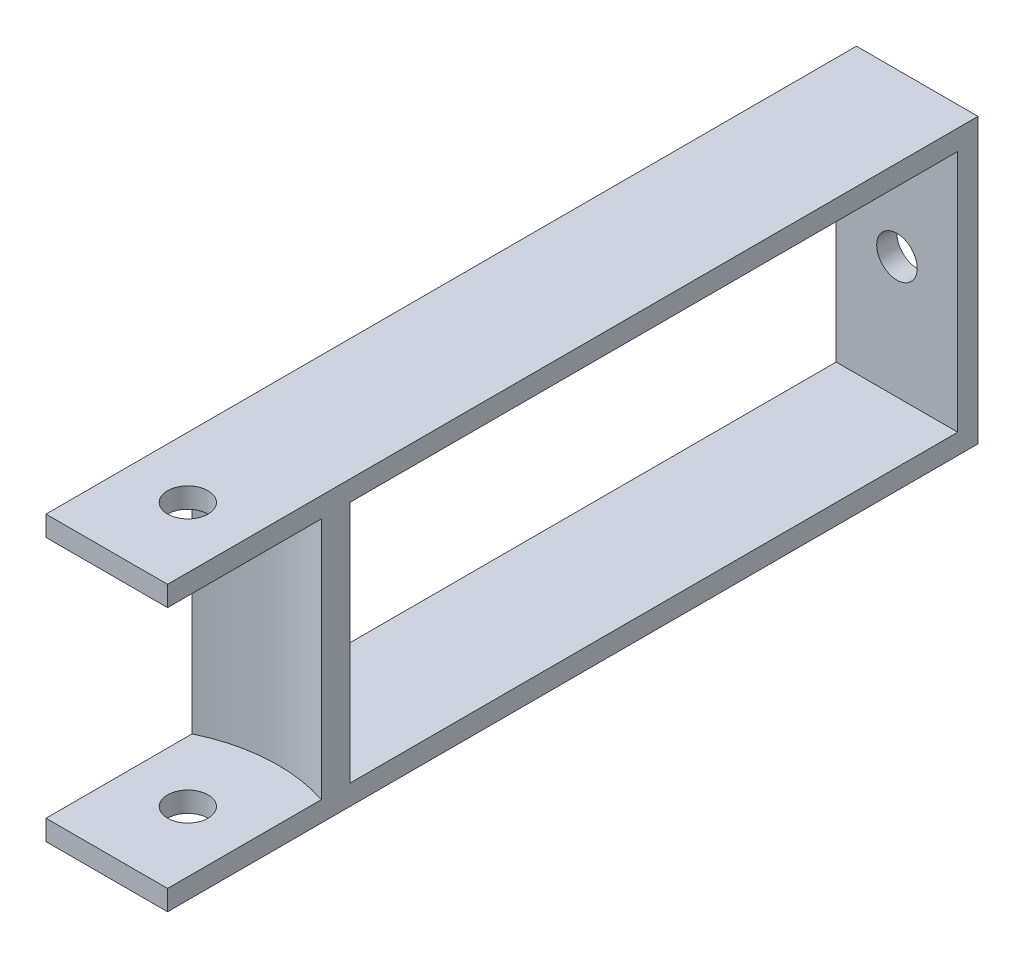
SolidWorks part; units mm, degrees
ref_plane "Alzado" through (0, 0, 0) normal (0, 0, 1) x (1, 0, 0)
ref_plane "Planta" through (0, 0, 0) normal (0, 1, 0) x (1, 0, 0)
ref_plane "Vista lateral" through (0, 0, 0) normal (1, 0, 0) x (0, 0, -1)
sketch "Croquis1" plane through (0, 0, 0) normal (0, 0, 1) x (1, 0, 0)
  line L1 (-10.0621, -21.7081) -> (19.9379, -21.7081)
  line L2 (-10.0621, -21.7081) -> (-10.0621, 48.2919)
  line L3 (-10.0621, 48.2919) -> (19.9379, 48.2919)
  line L4 (19.9379, -21.7081) -> (19.9379, 48.2919)
  dimension "D1" = 30
  dimension "D2" = 70
extrude "Saliente-Extruir1" add sketch "Croquis1" along normal blind 200
sketch "Croquis3" [suppressed] plane through (0, -21.7081, 0) normal (0, -1, 0) x (1, 0, 0)
  line L0 (19.9379, 200) -> (19.9379, 0) construction
  line L1 (-10.0621, 0) -> (19.9379, 0) construction
  circle A1 centre (4.9379, 180) radius 6.8739
  dimension "D1" = 15
  dimension "D2" = 180
extrude "Cortar-Extruir1" [suppressed] cut sketch "Croquis3" against normal through all contours A1
sketch "Croquis5" plane through (0, 0, 0) normal (0, 0, -1) x (-1, 0, 0)
  line L0 (-19.9379, -21.7081) -> (-19.9379, 48.2919) construction
  line L1 (10.0621, -21.7081) -> (-19.9379, -21.7081) construction
  circle A0 centre (-4.9379, 13.2919) radius 5
  dimension "D1" = 10
  dimension "D2" = 15
  dimension "D3" = 35
extrude "Cortar-Extruir2" cut sketch "Croquis5" against normal blind 20
ref_plane "Plano1" through (0, 13.2919, 0) normal (0, -1, 0) x (-1, 0, 0)
sketch "Croquis6" plane through (0, 13.2919, 0) normal (0, -1, 0) x (-1, 0, 0)
  line L0 (10.0621, -200) -> (-19.9379, -200) construction
  circle A0 centre (-7.2556, -200) radius 40
  dimension "D1" = 80
  dimension "D2" = 0
extrude "Cortar-Extruir3" cut sketch "Croquis6" against normal blind 30 and the other way blind 30 contours A0
ref_axis "z1" [suppressed] through (4.9379, 84.8388, 180) along (0, -1, 0)
sketch "Croquis7" plane through (-10.0621, 0, 0) normal (-1, 0, 0) x (0, 0, 1)
  line L0 (0, 48.2919) -> (0, -21.7081) construction
  line L1 (5, 43.2919) -> (155, 43.2919)
  line L2 (5, 43.2919) -> (5, -16.7081)
  line L3 (5, -16.7081) -> (155, -16.7081)
  line L4 (155, 43.2919) -> (155, -16.7081)
  line L5 (200, -21.7081) -> (0, -21.7081) construction
  dimension "D1" = 60
  dimension "D2" = 60
  dimension "D3" = 150
  dimension "D4" = 5
  dimension "D5" = 5
extrude "Cortar-Extruir4" cut sketch "Croquis7" against normal through all
sketch "Croquis8" plane through (0, -21.7081, 0) normal (0, -1, 0) x (-1, 0, 0)
  line L0 (10.0621, -200) -> (-19.9379, -200) construction
  line L1 (-19.9379, -200) -> (-19.9379, 0) construction
  circle A0 centre (-4.9379, -180) radius 5
  dimension "D1" = 10
  dimension "D2" = 20
  dimension "D3" = 15
extrude "Cortar-Extruir5" cut sketch "Croquis8" against normal through all
